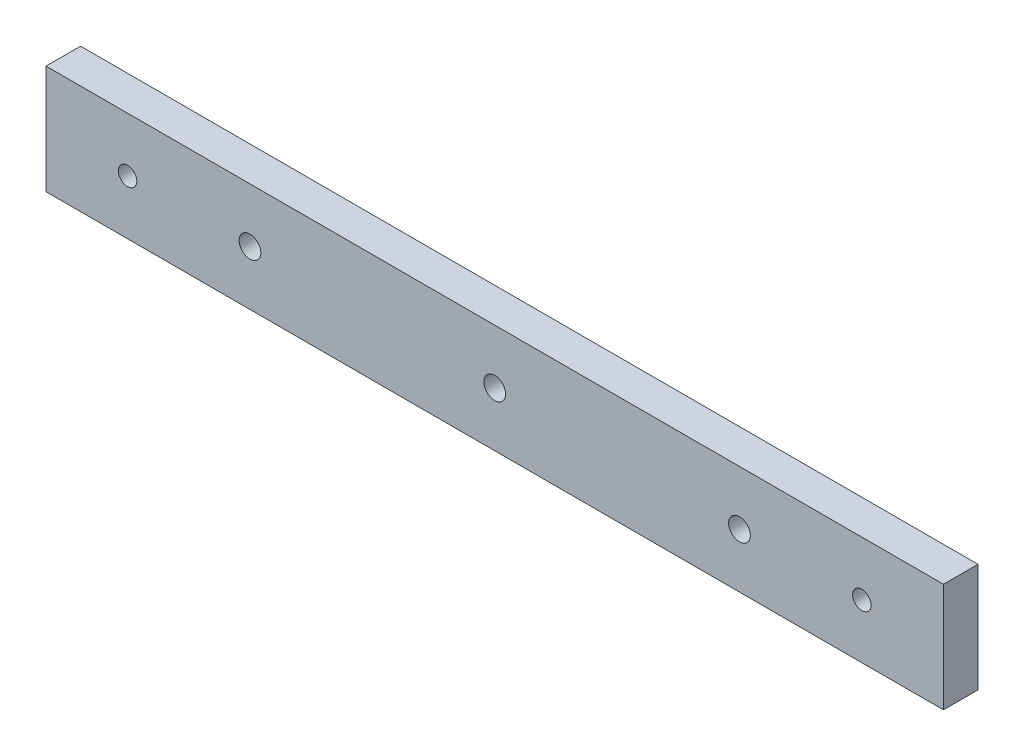
SolidWorks part; units mm, degrees
ref_plane "Front" through (0, 0, 0) normal (0, 0, 1) x (1, 0, 0)
ref_plane "Top" through (0, 0, 0) normal (0, 1, 0) x (1, 0, 0)
ref_plane "Right" through (0, 0, 0) normal (1, 0, 0) x (0, 0, -1)
sketch "Sketch1" plane through (0, 0, 0) normal (0, 0, 1) x (-1, 0, 0)
  line L0 (135.4523, 2.5754) -> (135.4523, 22.5754)
  line L1 (135.4523, 2.5754) -> (-29.5477, 2.5754)
  line L2 (135.4523, 22.5754) -> (-29.5477, 22.5754)
  line L3 (-29.5477, 2.5754) -> (-29.5477, 22.5754)
  circle A0 centre (-14.5477, 12.5754) radius 1.7
  circle A1 centre (120.4523, 12.5754) radius 1.7
  dimension "D4" = 20
  dimension "D1" = 165
  dimension "D2" = 15
  dimension "D3" = 15
  dimension "D5" = 10
  dimension "D6" = 10
extrude "Boss-Extrude1" add sketch "Sketch1" along normal blind 6.35 contours L3 L1 L0 L2 A1 A0 region at (-52.9523, -12.5754, 0)
sketch "Sketch3" plane through (0, 0, 0) normal (0, 0, -1) x (-1, 0, 0)
  line L0 (120.4523, -12.5754) -> (-14.5477, -12.5754)
  line L1 (120.4523, -12.5754) -> (75.4523, -12.5754)
  line L2 (75.4523, -12.5754) -> (30.4523, -12.5754)
  line L3 (30.4523, -12.5754) -> (-14.5477, -12.5754)
  line L4 (56.5023, -12.5754) -> (49.4023, -12.5754) construction
  line L5 (56.5023, -16.1254) -> (49.4023, -16.1254)
  line L6 (56.5023, -9.0254) -> (49.4023, -9.0254)
  line L7 (120.4523, -12.5754) -> (75.4523, -12.5754)
  line L8 (101.5023, -12.5754) -> (94.4023, -12.5754) construction
  line L9 (101.5023, -16.1254) -> (94.4023, -16.1254)
  line L10 (101.5023, -9.0254) -> (94.4023, -9.0254)
  line L11 (-14.5477, -12.5754) -> (30.4523, -12.5754)
  line L12 (11.5023, -12.5754) -> (4.4023, -12.5754) construction
  line L13 (11.5023, -16.1254) -> (4.4023, -16.1254)
  line L14 (11.5023, -9.0254) -> (4.4023, -9.0254)
  arc A0 (56.5023, -16.1254) -> (56.5023, -9.0254) centre (56.5023, -12.5754) ccw
  arc A1 (49.4023, -9.0254) -> (49.4023, -16.1254) centre (49.4023, -12.5754) ccw
  arc A2 (101.5023, -16.1254) -> (101.5023, -9.0254) centre (101.5023, -12.5754) ccw
  arc A3 (94.4023, -9.0254) -> (94.4023, -16.1254) centre (94.4023, -12.5754) ccw
  arc A4 (11.5023, -16.1254) -> (11.5023, -9.0254) centre (11.5023, -12.5754) ccw
  arc A5 (4.4023, -9.0254) -> (4.4023, -16.1254) centre (4.4023, -12.5754) ccw
  point P8 (52.9523, -12.5754)
  point P15 (97.9523, -12.5754)
  point P22 (7.9523, -12.5754)
  dimension "D3" = 3.55
  dimension "D6" = 3.55
  dimension "D8" = 3.55
  dimension "D1" = 45
  dimension "D2" = 45
  dimension "D4" = 7.1
  dimension "D5" = 7.1
  dimension "D7" = 7.1
extrude "Cut-Extrude2" cut sketch "Sketch3" against normal blind 3.35 contours L9 A3 L10 A2 | L5 A1 L6 A0 | L13 A5 L14 A4
sketch "Sketch4" plane through (0, 0, 3.35) normal (0, 0, -1) x (-1, 0, 0)
  line L0 (7.9523, -9.0254) -> (7.9523, -16.1254)
  line L1 (11.5023, -9.0254) -> (4.4023, -9.0254) construction
  line L2 (11.5023, -16.1254) -> (4.4023, -16.1254) construction
  line L3 (7.9523, -16.1254) -> (52.9523, -16.1254)
  line L4 (56.5023, -16.1254) -> (49.4023, -16.1254) construction
  line L5 (52.9523, -16.1254) -> (52.9523, -9.0254)
  line L6 (56.5023, -9.0254) -> (49.4023, -9.0254) construction
  line L7 (52.9523, -9.0254) -> (97.9523, -9.0254)
  line L8 (101.5023, -9.0254) -> (94.4023, -9.0254) construction
  line L9 (97.9523, -9.0254) -> (97.9523, -16.1254)
  line L10 (101.5023, -16.1254) -> (94.4023, -16.1254) construction
  circle A0 centre (97.9523, -12.5754) radius 2
  circle A1 centre (52.9523, -12.5754) radius 2
  circle A2 centre (7.9523, -12.5754) radius 2
extrude "Cut-Extrude3" cut sketch "Sketch4" against normal blind 3 contours L0 A2 | L0 A2 | L5 A1 | L5 A1 | L9 A0 | L9 A0 region at (-8.8011, -12.5754, 3.35) region at (-98.8011, -12.5754, 3.35) region at (-97.1035, -12.5754, 3.35) region at (-52.1035, -12.5754, 3.35) region at (-53.8011, -12.5754, 3.35) region at (-7.1035, -12.5754, 3.35)
